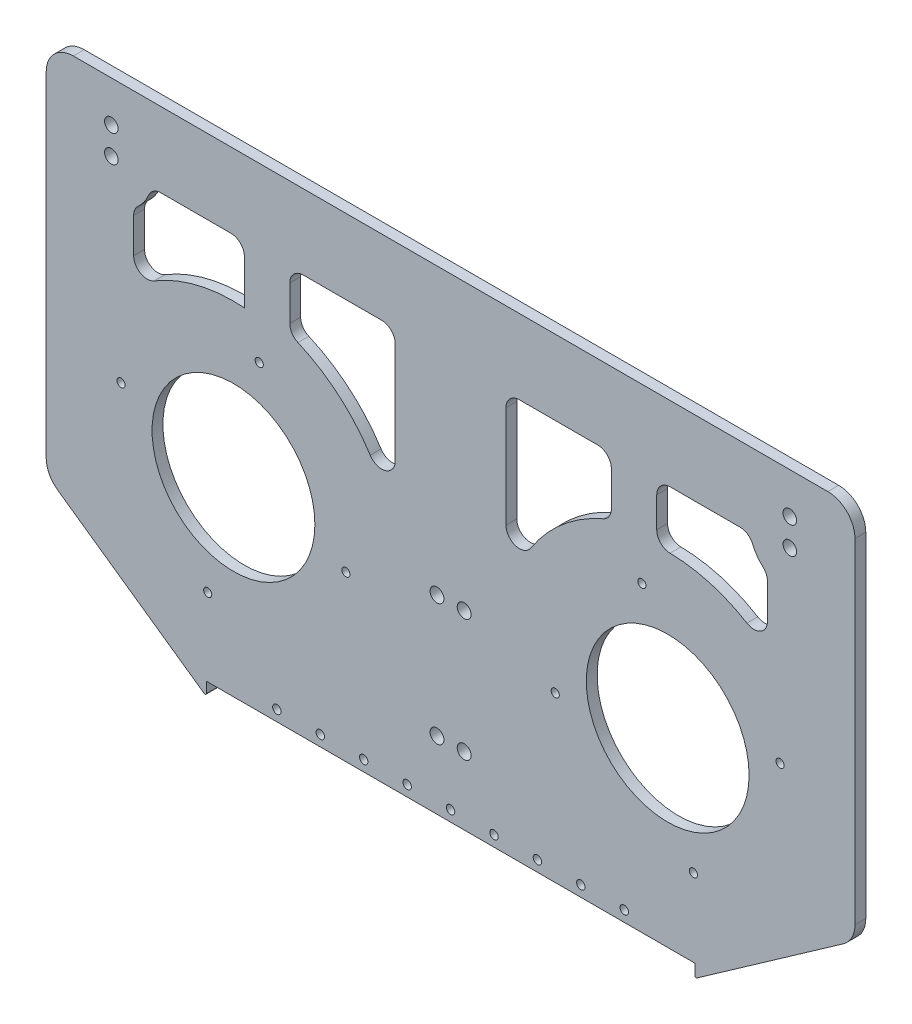
SolidWorks part; units mm, degrees
ref_plane "Front Plane" through (0, 0, 0) normal (0, 0, 1) x (1, 0, 0)
ref_plane "Top Plane" through (0, 0, 0) normal (0, 1, 0) x (1, 0, 0)
ref_plane "Right Plane" through (0, 0, 0) normal (1, 0, 0) x (0, 0, -1)
sketch "Sketch1" plane through (0, 0, 0) normal (0, 0, 1) x (1, 0, 0)
  line L0 (-125, 100) -> (125, 100) construction
  line L1 (-125, 0) -> (125, 0) construction
  line L2 (-145, -16.3871) -> (-90, -55) construction
  line L3 (-90, -55) -> (90, -55)
  line L4 (90, -55) -> (145, -16.3871) construction
  line L5 (-125, 105) -> (-125, 95) construction
  line L6 (0, -55) -> (0, 100) construction
  line L7 (-145, 120) -> (145, 120)
  line L8 (145, 120) -> (145, -16.3871) construction
  line L11 (-145, -16.3871) -> (-145, 120) construction
  line L12 (125, 105) -> (125, 95) construction
  line L14 (-149, 120) -> (-149, -18.4662)
  line L15 (-149, -18.4662) -> (-90, -59.8873)
  line L16 (-90, -59.8873) -> (-90, -55)
  line L17 (-90, -59.8873) -> (-90, -55)
  line L18 (-149, 120) -> (-145, 120)
  line L19 (90, -59.8873) -> (90, -55)
  line L20 (149, 120) -> (145, 120)
  line L21 (149, -18.4662) -> (90, -59.8873)
  line L22 (149, 120) -> (149, -18.4662)
  circle A0 centre (-125, 100) radius 12.5 construction
  circle A10 centre (-125, 0) radius 12.5 construction
  circle A11 centre (125, 0) radius 12.5 construction
  circle A12 centre (-125, 0) radius 17.5 construction
  circle A13 centre (-125, 100) radius 17.5 construction
  circle A25 centre (-125, 95) radius 2.5
  circle A26 centre (-125, 105) radius 2.5
  circle A27 centre (125, 95) radius 2.5
  circle A28 centre (125, 105) radius 2.5
  circle A32 centre (5, 15) radius 2.55
  circle A33 centre (5, -30) radius 2.55
  circle A34 centre (-5, -30) radius 2.55
  circle A35 centre (-5, 15) radius 2.55
  point P12 (0, 100)
  point P15 (0, -34.3933)
  point P22 (0, 0)
  point P45 (0, 120)
  dimension "D1" = 25
  dimension "D2" = 5
  dimension "D17" = 5.1
  dimension "D4" = 100
  dimension "D6" = 5
  dimension "D11" = 20
  dimension "D12" = 20
  dimension "D7" = 10
  dimension "D8" = 250
  dimension "D9" = 180
  dimension "D10" = 144.929
  dimension "D13" = 4
  dimension "D14" = 4
  dimension "D15" = 5
  dimension "D16" = 45
  dimension "D3" = 25
  dimension "D18" = 175
extrude "Boss-Extrude1" add sketch "Sketch1" along normal blind 4 contours L22 L20 L7 L18 L14 L15 L16 L3 L19 L21 A27 A26 A25 A28 region at (0, 35.2559, 0)
sketch "Sketch2" plane through (0, 0, 4) normal (0, 0, 1) x (1, 0, 0)
  line L0 (121.4264, 24.4924) -> (38.5736, 5.5076) construction
  line L1 (89.4924, -26.4264) -> (70.5076, 56.4264) construction
  line L2 (0, 0) -> (0, 120) construction
  line L5 (-80, 15) -> (80, 15) construction
  line L6 (-5, 15) -> (5, 15) construction
  line L8 (-149, 120) -> (-149, -18.4662) construction
  line L9 (149, 120) -> (-149, 120) construction
  circle A0 centre (80, 15) radius 42.5 construction
  circle A1 centre (38.5736, 5.5076) radius 1.5
  circle A2 centre (70.5076, 56.4264) radius 1.5
  circle A3 centre (121.4264, 24.4924) radius 1.5
  circle A4 centre (89.4924, -26.4264) radius 1.5
  circle A5 centre (80, 15) radius 30
  circle A6 centre (-38.5736, 5.5076) radius 1.5
  circle A7 centre (-70.5076, 56.4264) radius 1.5
  circle A8 centre (-89.4924, -26.4264) radius 1.5
  circle A9 centre (-121.4264, 24.4924) radius 1.5
  circle A10 centre (-80, 15) radius 42.5 construction
  circle A11 centre (-80, 15) radius 30
  circle A12 centre (-80, 15) radius 47.5 construction
  point P6 (80, 15)
  point P27 (-80, 15)
  point P30 (0, 15)
  point P35 (0, 0)
  point P36 (0, 120)
  dimension "D1" = 85
  dimension "D2" = 3
  dimension "D3" = 60
  dimension "D4" = 95
  dimension "D5" = 69
  dimension "D6" = 41.4264
  dimension "D7" = 105
  dimension "D8" = 10
extrude "Cut-Extrude1" cut sketch "Sketch2" against normal blind 10 contours A11 | A5 | A7 | A9 | A8 | A2 | A1 | A3 | A4 | A6 region at (38.5736, 5.5076, 4) region at (70.5076, 56.4264, 4) region at (121.4264, 24.4924, 4) region at (89.4924, -26.4264, 4) region at (80, 15, 4) region at (-70.5076, 56.4264, 4) region at (-89.4924, -26.4264, 4) region at (-121.4264, 24.4924, 4) region at (-80, 15, 4)
sketch "Sketch3" plane through (0, 0, 4) normal (0, 0, 1) x (1, 0, 0)
  line L1 (-90, -59.8873) -> (-90, -55) construction
  line L3 (-90, -55) -> (90, -55) construction
  circle A4 centre (-64, -51) radius 1.55
  circle A5 centre (-48, -51) radius 1.55
  circle A6 centre (-32, -51) radius 1.55
  circle A7 centre (-16, -51) radius 1.55
  circle A8 centre (0, -51) radius 1.55
  circle A9 centre (16, -51) radius 1.55
  circle A10 centre (32, -51) radius 1.55
  circle A11 centre (48, -51) radius 1.55
  circle A12 centre (64, -51) radius 1.55
  point P0 (0, 0)
  dimension "D2" = 3.1
  dimension "D1" = 4
  dimension "D3" = 26
  dimension "D5" = 9
extrude "Cut-Extrude2" cut sketch "Sketch3" against normal through all contours A4 | A5 | A6 | A12 | A11 | A10 | A7 | A8 | A9 region at (-64, -51, 4) region at (-48, -51, 4) region at (-32, -51, 4) region at (32, -51, 4) region at (48, -51, 4) region at (64, -51, 4)
sketch "Sketch6" plane through (0, 0, 0) normal (0, 0, -1) x (-1, 0, 0)
  line L0 (-20.3921, 20.3957) -> (-20.3921, 92.4562)
  line L1 (-20.3921, 92.4562) -> (-59.2398, 92.4562)
  line L2 (-59.2398, 92.4562) -> (-59.2398, 71.1358)
  line L3 (-75.9623, 92.4562) -> (-110.4197, 92.4562)
  line L4 (-75.9623, 92.4562) -> (-75.9623, 71.1358)
  line L5 (-116.7764, 82.6944) -> (-116.7764, 57.603)
  line L6 (0, -55) -> (0, 120) construction
  line L7 (90, -55) -> (-90, -55) construction
  line L8 (-145, 120) -> (145, 120) construction
  line L9 (20.3921, 20.3957) -> (20.3921, 92.4562)
  line L10 (20.3921, 92.4562) -> (59.2398, 92.4562)
  line L11 (59.2398, 92.4562) -> (59.2398, 71.1358)
  line L12 (75.9623, 92.4562) -> (75.9623, 71.1358)
  line L13 (75.9623, 92.4562) -> (110.4197, 92.4562)
  line L14 (116.7764, 82.6944) -> (116.7764, 57.603)
  arc A0 (-20.3921, 20.3957) -> (-59.2398, 71.1358) centre (-80, 15) ccw
  arc A1 (-75.9623, 71.1358) -> (-116.7764, 57.603) centre (-80, 15) ccw
  arc A2 (-110.4197, 92.4562) -> (-116.7764, 82.6944) centre (-125, 95) cw
  arc A3 (20.3921, 20.3957) -> (59.2398, 71.1358) centre (80, 15) cw
  arc A4 (75.9623, 71.1358) -> (116.7764, 57.603) centre (80, 15) cw
  arc A5 (110.4197, 92.4562) -> (116.7764, 82.6944) centre (125, 95) ccw
extrude "Cut-Extrude3" cut sketch "Sketch6" against normal through all contours L3 A2 L5 A1 L4 | A0 L0 L1 L2 | L9 A3 L11 L10 | A5 L13 L12 A4 L14 region at (36.1386, 72.1325, 0) region at (97.4759, 79.2288, 0) region at (-36.1386, 72.1325, 0) region at (-97.4759, 79.2288, 0)
fillet "Fillet1" radius 5 17 edges at (-59.2398, 92.4562, 2) (-110.4197, 92.4562, 2) (-116.7764, 82.6944, 2) (-59.2398, 71.1358, 2) (-116.7764, 57.603, 2) (-75.9623, 92.4562, 2) (-20.3921, 92.4562, 2) (-20.3921, 20.3957, 2) (20.3921, 20.3957, 2) (59.2398, 92.4562, 2) (59.2398, 71.1358, 2) (20.3921, 92.4562, 2) (75.9623, 92.4562, 2) (75.9623, 71.1358, 2) (110.4197, 92.4562, 2) (116.7764, 82.6944, 2) (116.7764, 57.603, 2)
fillet "Fillet2" radius 0.5 2 edges at (90, -59.8873, 2) (-90, -59.8873, 2)
fillet "Fillet3" radius 10 4 edges at (149, -18.4662, 2) (149, 120, 2) (-149, 120, 2) (-149, -18.4662, 2)
equation "\"D1@Sketch1\" = \"cf_tube_outer_diameter\""
equation "\"mid_plate_mid_to_top\" = 100mm"
equation "\"mid_plate_mid_to_bottom\" = 30mm"
equation "\"mid_plate_horizontal_spacing\"=250mm"
equation "\"cf_tube_outer_diameter\"= 25mm"
equation "\"D4@Sketch1\"=\"mid_plate_mid_to_top\""
equation "\"cf_tube_inner_diameter\" = 21mm"
equation "\"mid_tube_length\" = 121mm"
equation "\"cf_plate_thickness\" =4mm"
equation "\"D1@Boss-Extrude1\"=\"cf_plate_thickness\""
equation "\"D8@Sketch1\"=\"mid_plate_horizontal_spacing\""
equation "\"mid_plate_bottom_width\" = 180mm"
equation "\"D9@Sketch1\"=\"mid_plate_bottom_width\""
equation "\"mid_support_plate_distance\" = 250mm"
equation "\"nut_strip_2_hole_distance\" = 7mm"
equation "\"nut_strip_hole_diameter\" = 2.5mm"
equation "\"nut_strip_hole_to_edge_distance\"= 2.5mm"
